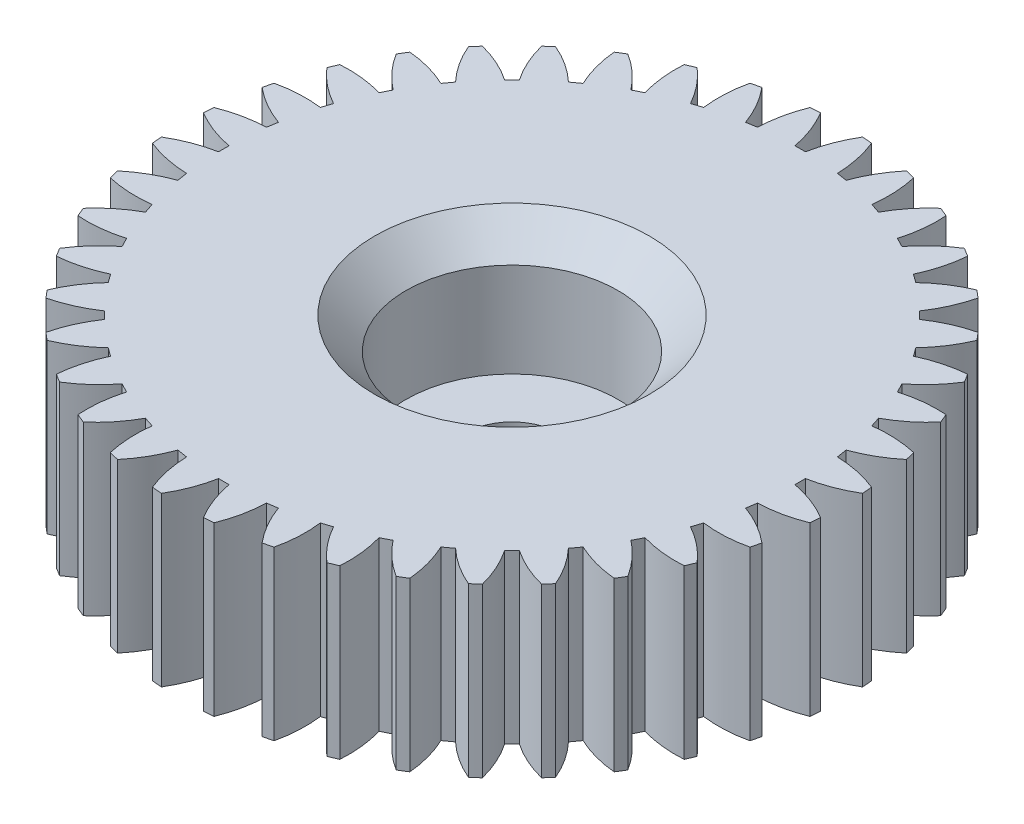
SolidWorks part; units mm, degrees
ref_plane "Front Plane" through (0, 0, 0) normal (0, 0, 1) x (1, 0, 0)
ref_plane "Top Plane" through (0, 0, 0) normal (0, 1, 0) x (1, 0, 0)
ref_plane "Right Plane" through (0, 0, 0) normal (1, 0, 0) x (0, 0, -1)
sketch "Sketch1" plane through (0, 0, 0) normal (0, 1, 0) x (1, 0, 0)
  line L0 (0, 0) -> (0, 7.875) construction
  circle A0 centre (0, 0) radius 7.875
  circle A1 centre (0, 0) radius 6.875
  arc A2 (0.125, 6.8739) -> (0.5, 7.8591) centre (3.0727, 6.3159) cw
  arc A3 (-0.125, 6.8739) -> (-0.5, 7.8591) centre (-3.0727, 6.3159) ccw
  circle A4 centre (0, 0) radius 2.525
  circle A5 centre (0, 0) radius 1.125
  dimension "D1" = 15.75
  dimension "D2" = 1
  dimension "D4" = 3
  dimension "D5" = 5.05
  dimension "D6" = 2.25
  dimension "D3" = 0.5
  dimension "D7" = 0.125
extrude "Boss-Extrude1" add sketch "Sketch1" along normal blind 1 contours A5 A4 region at (-2.4536, 0, 0)
extrude "Boss-Extrude2" add sketch "Sketch1<3>" along normal blind 4 contours A4 A1 | A1 A0 A2 | A0 | A1 region at (-5.2364, 0, 5.5802) region at (4.7666, 0, -4.6807)
sketch "Sketch1<3>" plane through (0, 0, 0) normal (0, 1, 0) x (1, 0, 0) same geometry as "Sketch1"
extrude "Cut-Extrude1" cut sketch "Sketch1<5>" along normal through all contours L0 A0 | L0 A2 A0 region at (0, 0, -7.4836)
sketch "Sketch1<5>" plane through (0, 0, 0) normal (0, 1, 0) x (1, 0, 0) same geometry as "Sketch1"
pattern_circular "CirPattern3" count 40 over 360 about axis through (0, 4, 0) along (0, -1, 0) of "Cut-Extrude1"
chamfer "Chamfer1" distance 0.75 angle 45 1 edges at (0, 4, 2.525)
